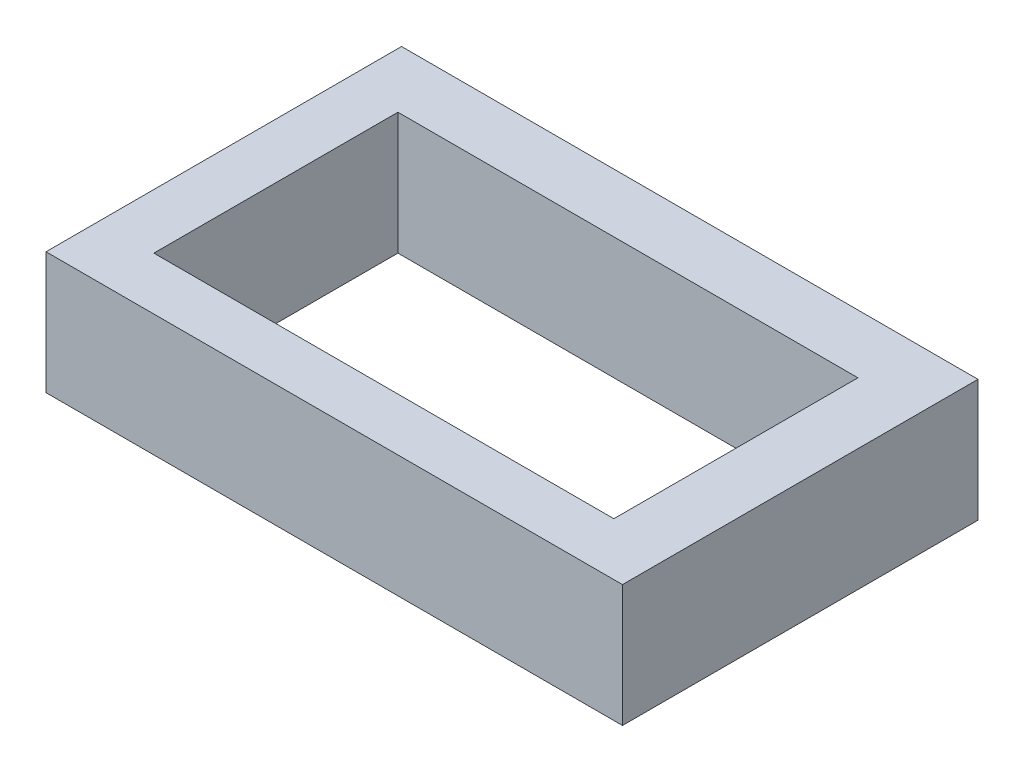
SolidWorks part; units mm, degrees
ref_plane "Front Plane" through (0, 0, 0) normal (0, 0, 1) x (1, 0, 0)
ref_plane "Top Plane" through (0, 0, 0) normal (0, 1, 0) x (1, 0, 0)
ref_plane "Right Plane" through (0, 0, 0) normal (1, 0, 0) x (0, 0, -1)
sketch "Sketch1" plane through (0, 0, 0) normal (0, 1, 0) x (1, 0, 0)
  line L1 (15.216, 27.9688) -> (39.716, 27.9688)
  line L2 (15.216, 27.9688) -> (15.216, 14.9688)
  line L3 (15.216, 14.9688) -> (39.716, 14.9688)
  line L4 (39.716, 27.9688) -> (39.716, 14.9688)
  line L5 (12.281, 31.0961) -> (42.9837, 31.0961)
  line L6 (12.281, 31.0961) -> (12.281, 12.1599)
  line L7 (12.281, 12.1599) -> (42.9837, 12.1599)
  line L8 (42.9837, 31.0961) -> (42.9837, 12.1599)
  point P8 (0, 0)
  point P9 (43.0828, 3.7866)
  point P10 (12.6709, 4.5527)
  point P11 (13.2454, 4.591)
  point P12 (0, 0)
  point P13 (0, 0)
  point P14 (0, 0)
  point P15 (42.9837, 12.2371)
  point P16 (12.281, 12.1599)
  dimension "D1" = 24.5
  dimension "D2" = 13
extrude "Boss-Extrude1" add sketch "Sketch1" along normal blind 6.5
